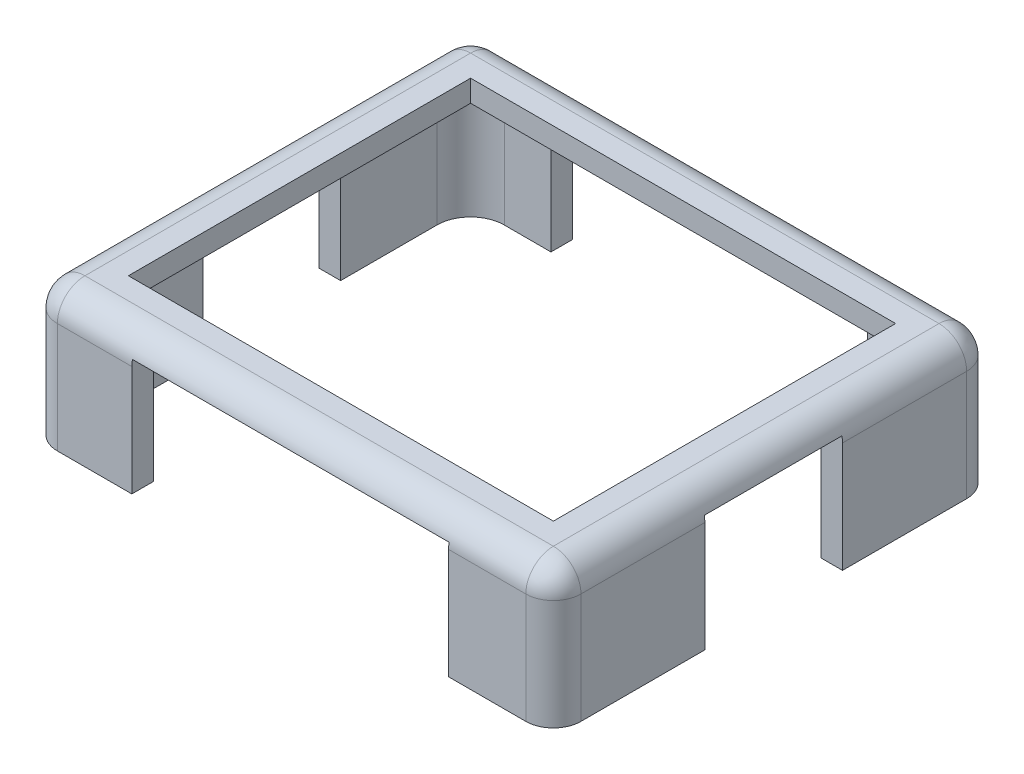
SolidWorks part; units mm, degrees
ref_plane "Front Plane" through (0, 0, 0) normal (0, 0, 1) x (1, 0, 0)
ref_plane "Top Plane" through (0, 0, 0) normal (0, 1, 0) x (1, 0, 0)
ref_plane "Right Plane" through (0, 0, 0) normal (1, 0, 0) x (0, 0, -1)
sketch "Sketch1" plane through (0, 0, 0) normal (0, 1, 0) x (1, 0, 0)
  line L1 (24.1046, 20.2946) -> (-24.1046, 20.2946)
  line L2 (24.1046, 20.2946) -> (24.1046, -20.2946)
  line L3 (24.1046, -20.2946) -> (-24.1046, -20.2946)
  line L4 (-24.1046, 20.2946) -> (-24.1046, -20.2946)
  line L5 (24.1046, 20.2946) -> (-24.1046, -20.2946) construction
  line L6 (24.1046, -20.2946) -> (-24.1046, 20.2946) construction
  point P0 (0, 0)
  dimension "D1" = 40.5892
  dimension "D2" = 48.2092
extrude "Boss-Extrude1" add sketch "Sketch1" along normal blind 12.7
shell "Shell1" thickness 2 removed face at (0, 0, 0)
sketch "Sketch3" plane through (0, 0, 20.2946) normal (0, 0, 1) x (1, 0, 0)
  line L3 (-12.1666, 10.6985) -> (-14.7066, 10.6985)
  line L12 (-24.1046, 0) -> (24.1046, 0) construction
  line L13 (-14.7066, 10.6985) -> (14.4526, 10.6985)
  line L14 (-14.7066, 10.6985) -> (-14.7066, 0)
  line L15 (-14.7066, 0) -> (14.4526, 0)
  line L16 (14.4526, 10.6985) -> (14.4526, 0)
  point P6 (0, 0)
  point P8 (-24.1046, 0)
  line M10 (-24.1046, 0) -> (24.1046, 0)
sketch "Sketch4" plane through (-24.1046, 0, 0) normal (-1, 0, 0) x (0, 0, 1)
  line L3 (0, 0) -> (6.35, 0)
  line L4 (-20.2946, 0) -> (20.2946, 0) construction
  line L9 (6.35, 0) -> (6.35, 10.6985)
  line L10 (6.35, 10.6985) -> (-6.3246, 10.6985)
  line L11 (-6.3246, 0) -> (0, 0)
  line L12 (-6.3246, 10.6985) -> (-6.3246, 0)
  dimension "D1" = 6.35
  dimension "D3" = 10.6985
extrude "Cut-Extrude2" cut sketch "Sketch4" against normal blind 68.58
fillet "Fillet6" radius 2.54 4 edges at (0, 12.7, -20.2946) (24.1046, 12.7, 0) (0, 12.7, 20.2946) (-24.1046, 12.7, 0)
fillet "Fillet7" radius 2.54 2 edges at (-23.3607, 11.9561, -19.5507) (-24.1046, 5.08, -20.2946)
fillet "Fillet8" radius 2.54 2 edges at (-23.3607, 11.9561, 19.5507) (-24.1046, 5.08, 20.2946)
fillet "Fillet9" radius 2.54 2 edges at (23.3607, 11.9561, -19.5507) (24.1046, 5.08, -20.2946)
fillet "Fillet10" radius 2.54 2 edges at (23.3607, 11.9561, 19.5507) (24.1046, 5.08, 20.2946)
sketch "Sketch6" plane through (0, 12.7, 0) normal (0, 1, 0) x (1, 0, 0)
  line L0 (-21.5646, 17.7546) -> (-21.5646, -17.7546) construction
  line L1 (-19.5646, 15.7546) -> (19.5646, 15.7546)
  line L2 (-19.5646, 15.7546) -> (-19.5646, -15.7546)
  line L3 (-19.5646, -15.7546) -> (19.5646, -15.7546)
  line L4 (19.5646, 15.7546) -> (19.5646, -15.7546)
  line L6 (21.5646, 17.7546) -> (-21.5646, 17.7546) construction
  line L7 (-21.5646, -17.7546) -> (21.5646, -17.7546) construction
  line L8 (21.5646, -17.7546) -> (21.5646, 17.7546) construction
  dimension "D1" = 2
  dimension "D2" = 2
  dimension "D3" = 2
  dimension "D4" = 2
extrude "Cut-Extrude4" cut sketch "Sketch6" against normal blind 68.58
extrude "Cut-Extrude5" cut sketch "Sketch3" against normal blind 49.276 contours L16 L13 L3 L14 M10 region at (-0.127, 5.3492, 20.2946)
fillet "Fillet19" radius 3.0988 4 edges at (-22.1046, 5.35, -18.2946) (22.1046, 5.35, -18.2946) (22.1046, 5.35, 18.2946) (-22.1046, 5.35, 18.2946)
